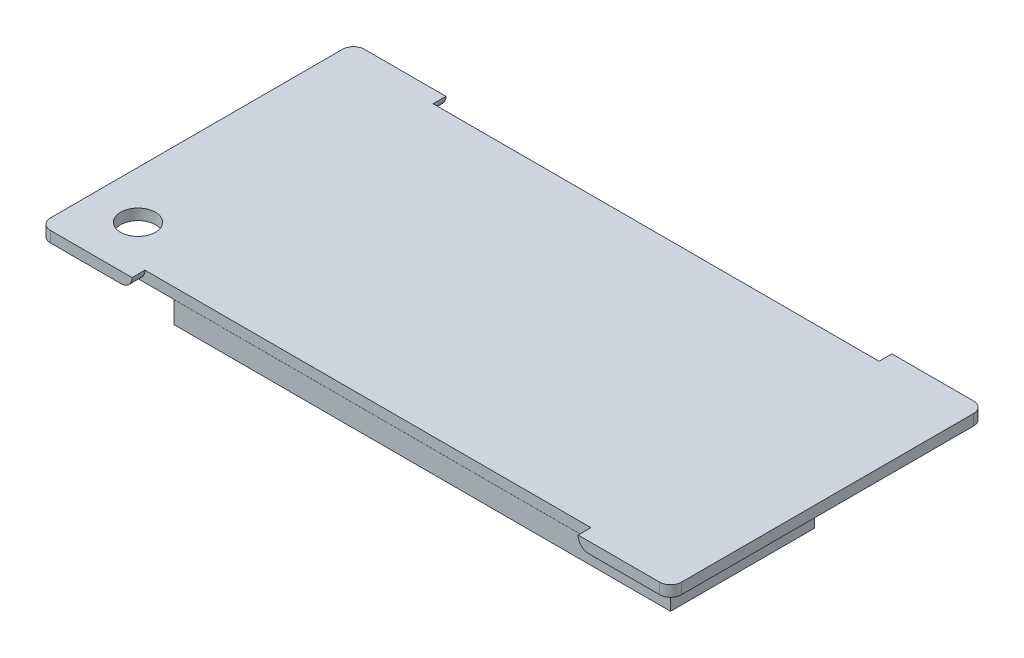
SolidWorks part; units mm, degrees
ref_plane "Front Plane" through (0, 0, 0) normal (0, 0, 1) x (1, 0, 0)
ref_plane "Top Plane" through (0, 0, 0) normal (0, 1, 0) x (1, 0, 0)
ref_plane "Right Plane" through (0, 0, 0) normal (1, 0, 0) x (0, 0, -1)
sketch "Sketch1"
sketch "Sketch2" plane through (0, 0, 0) normal (0, 1, 0) x (1, 0, 0)
  line L0 (-28, 14.425) -> (28, 14.425)
  line L1 (-27.5, 12.925) -> (27.5, 12.925) construction
  line L2 (-27.5, 12.925) -> (-27.5, -12.925) construction
  line L3 (-27.5, -12.925) -> (27.5, -12.925) construction
  line L4 (27.5, 12.925) -> (27.5, -12.925) construction
  line L5 (29, 13.425) -> (29, -13.425)
  line L6 (-28, -14.425) -> (28, -14.425)
  line L7 (-29, 13.425) -> (-29, -13.425)
  line L8 (-27.5, -12.925) -> (27.5, 12.925) construction
  line L9 (-29, 14.425) -> (29, 14.425) construction
  line L10 (29, 14.425) -> (29, -14.425) construction
  line L11 (-29, -14.425) -> (29, -14.425) construction
  line L12 (-29, 14.425) -> (-29, -14.425) construction
  arc A0 (28, 14.425) -> (29, 13.425) centre (28, 13.425) cw
  arc A1 (29, -13.425) -> (28, -14.425) centre (28, -13.425) cw
  arc A2 (-28, -14.425) -> (-29, -13.425) centre (-28, -13.425) cw
  arc A3 (-28, 14.425) -> (-29, 13.425) centre (-28, 13.425) ccw
  point P8 (0, 0)
  point P12 (0, 0)
  dimension "D4" = 1
  dimension "D1" = 55
  dimension "D2" = 25.85
  dimension "D3" = 1.5
sketch "Sketch20" plane through (0, 0, 0) normal (0, 1, 0) x (1, 0, 0)
  line L1 (-28, 14.425) -> (-20.5, 14.425)
  line L2 (-29, 13.425) -> (-29, -13.425)
  line L3 (-28, -14.425) -> (-20.5, -14.425)
  line L4 (29, 13.425) -> (29, -13.425)
  line L6 (-20.5, 14.425) -> (-20.5, 13.245)
  line L7 (-20.5, 13.245) -> (20.5, 13.245)
  line L8 (20.5, 14.425) -> (20.5, 13.245)
  line L9 (20.5, 14.425) -> (28, 14.425)
  line L10 (20.5, -14.425) -> (28, -14.425)
  line L12 (-20.5, -14.425) -> (-20.5, -13.245)
  line L13 (-20.5, -13.245) -> (20.5, -13.245)
  line L14 (20.5, -14.425) -> (20.5, -13.245)
  line L15 (-29, 0) -> (29, 0) construction
  arc A0 (28, 14.425) -> (29, 13.425) centre (28, 13.425) cw
  arc A1 (28, -14.425) -> (29, -13.425) centre (28, -13.425) ccw
  arc A2 (-29, -13.425) -> (-28, -14.425) centre (-28, -13.425) ccw
  arc A3 (-28, 14.425) -> (-29, 13.425) centre (-28, 13.425) ccw
  point P15 (29, 14.425)
  point P18 (29, -14.425)
  point P23 (-29, 14.425)
  point P24 (0, 13.245)
  point P28 (0, 0)
  point P29 (0, -13.245)
  dimension "D6" = 1
  dimension "D1" = 58
  dimension "D2" = 28.85
  dimension "D3" = 1.18
  dimension "D4" = 41
  dimension "D5" = 1.18
  dimension "D7" = 41
extrude "Boss-Extrude10" add sketch "Sketch20" along normal blind 1 separate body
sketch "Sketch21" plane through (0, 0, 0) normal (0, -1, 0) x (1, 0, 0)
  line L3 (-27.825, 3.25) -> (-26.825, 3.25)
  line L4 (-17.825, 13.25) -> (-17.825, 12.25)
  line L30 (27.825, 13.25) -> (-17.825, 13.25)
  line L31 (27.825, 0) -> (27.825, 13.25)
  line L32 (26.825, 0) -> (27.825, 0)
  line L33 (26.825, 12.25) -> (26.825, 0)
  line L34 (-17.825, 12.25) -> (26.825, 12.25)
  line L35 (-26.825, -12.25) -> (-26.825, 3.25)
  line L36 (16.5, -12.25) -> (-26.825, -12.25)
  line L37 (16.5, -13.25) -> (16.5, -12.25)
  line L38 (-27.825, -13.25) -> (16.5, -13.25)
  line L39 (-27.825, 3.25) -> (-27.825, -13.25)
  dimension "D5" = 12.25
  dimension "D6" = 13.25
  dimension "D7" = 1
  dimension "D8" = 1
  dimension "D9" = 43.325
  dimension "D10" = 44.325
  dimension "D11" = 10
  dimension "D13" = 27.825
extrude "Boss-Extrude11" add sketch "Sketch21" along normal blind 2
fillet "Fillet1" radius 1 4 edges at (-20.5, 0, -13.8375) (20.5, 0, -13.835) (20.5, 0, 13.8375) (-20.5, 0, 13.835)
sketch "Sketch22" plane through (0, 0, 0) normal (0, -1, 0) x (1, 0, 0)
  circle A0 centre (-24.6275, 9.7505) radius 1.6
  point P2 (-24.6275, 9.7505)
  dimension "D1" = 3.2
extrude "Cut-Extrude1" cut sketch "Sketch22" against normal blind 10
